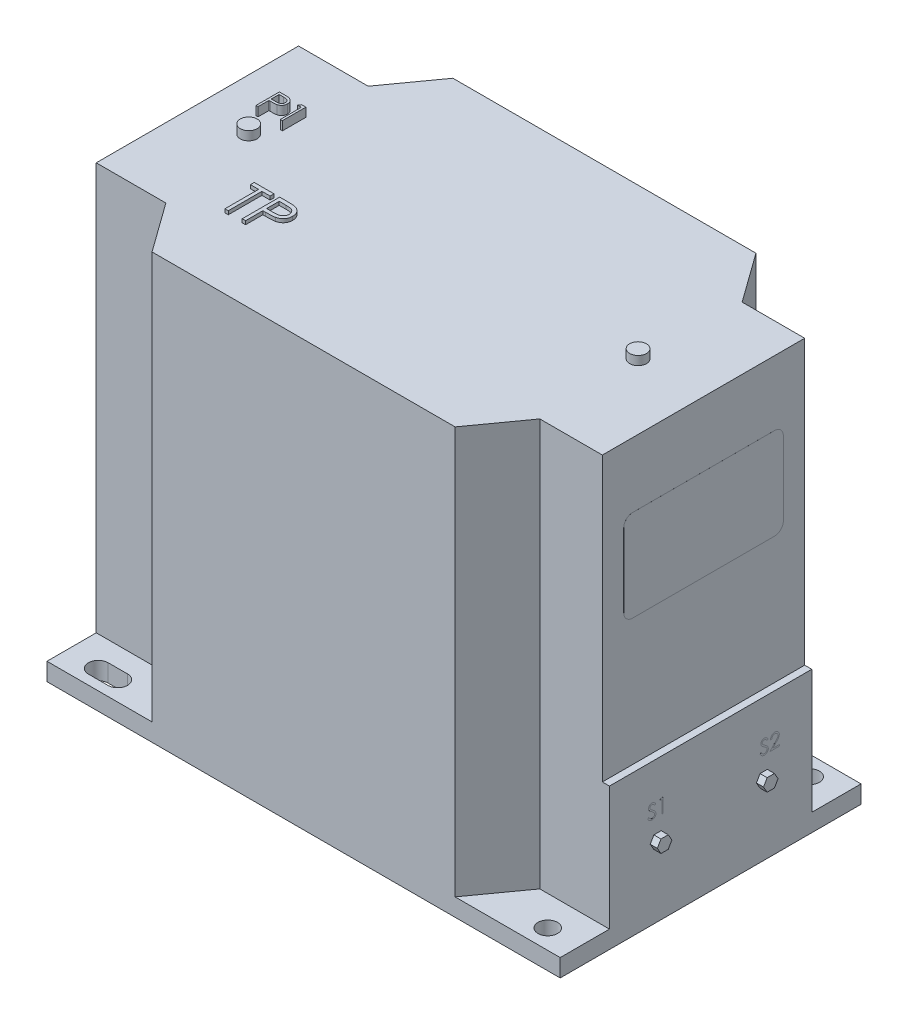
SolidWorks part; units mm, degrees
ref_plane "Alzado" through (0, 0, 0) normal (0, 0, 1) x (1, 0, 0)
ref_plane "Planta" through (0, 0, 0) normal (0, 1, 0) x (1, 0, 0)
ref_plane "Vista lateral" through (0, 0, 0) normal (1, 0, 0) x (0, 0, -1)
sketch "Croquis1" plane through (0, 0, 0) normal (0, 1, 0) x (1, 0, 0)
  line L1 (-145, 85) -> (145, 85)
  line L2 (-145, 85) -> (-145, -85)
  line L3 (-145, -85) -> (145, -85)
  line L4 (145, 85) -> (145, -85)
  line L5 (-145, 85) -> (145, -85) construction
  line L6 (-145, -85) -> (145, 85) construction
  point P0 (0, 0)
  dimension "D1" = 290
  dimension "D2" = 170
extrude "Saliente-Extruir1" add sketch "Croquis1" along normal blind 240
sketch "Croquis2" plane through (0, 240, 0) normal (0, 1, 0) x (1, 0, 0)
  line L0 (0, 0) -> (145, 0) construction
  line L1 (145, -85) -> (145, 85) construction
  line L2 (0, 0) -> (0, 85) construction
  line L3 (145, 85) -> (-145, 85) construction
  line L4 (-127, 74) -> (-116, 74) construction
  line L5 (-127, 79.5) -> (-116, 79.5)
  line L6 (-127, 68.5) -> (-116, 68.5)
  line L7 (-127, -74) -> (-116, -74) construction
  line L8 (-127, -79.5) -> (-116, -79.5)
  line L9 (-127, -68.5) -> (-116, -68.5)
  line L10 (-145, 57.1591) -> (-105.6531, 57.1591)
  line L11 (-145, 85) -> (-145, -85) construction
  line L12 (-105.6531, 57.1591) -> (-85.6261, 85)
  line L13 (145, 57.1591) -> (105.6531, 57.1591)
  line L14 (105.6531, 57.1591) -> (85.6261, 85)
  line L15 (145, -57.1591) -> (105.6531, -57.1591)
  line L16 (105.6531, -57.1591) -> (85.6261, -85)
  line L17 (-105.6531, -57.1591) -> (-85.6261, -85)
  line L18 (-145, -57.1591) -> (-105.6531, -57.1591)
  circle A0 centre (127, 74) radius 5.5
  circle A1 centre (127, -74) radius 5.5
  arc A2 (-127, 79.5) -> (-127, 68.5) centre (-127, 74) ccw
  arc A3 (-116, 68.5) -> (-116, 79.5) centre (-116, 74) ccw
  arc A4 (-127, -79.5) -> (-127, -68.5) centre (-127, -74) cw
  arc A5 (-116, -68.5) -> (-116, -79.5) centre (-116, -74) cw
  point P14 (-121.5, 74)
  point P22 (-121.5, -74)
  line M9 (145, -85) -> (145, 85)
  line M10 (145, 85) -> (-145, 85)
  line M11 (-145, 85) -> (-145, -85)
  line M12 (-145, -85) -> (145, -85)
  dimension "D1" = 11
  dimension "D2" = 74
  dimension "D3" = 127
  dimension "D4" = 11
  dimension "D5" = 254
  dimension "D6" = 11
extrude "Cortar-Extruir1" cut sketch "Croquis2" against normal blind 230 contours L18 L17 L9 A5 L8 A4 M11 M12 | L10 L12 A3 L6 A2 L5 M10 M11 | L14 L13 A0 M9 M10 | L15 L16 A1 M12 M9 region at (-144.3442, 240, -71.0796) region at (-125.3265, 240, 57.8149) region at (119.4598, 240, -71.8739) region at (119.4598, 240, 71.8739)
sketch "Croquis3" plane through (0, 240, 0) normal (0, 1, 0) x (1, 0, 0)
  line L0 (-127, 74) -> (-116, 74) construction
  line L1 (-127, 79.5) -> (-116, 79.5)
  line L2 (-127, 68.5) -> (-116, 68.5)
  line L3 (-127, -74) -> (-116, -74) construction
  line L4 (-127, -68.4262) -> (-116, -68.4262)
  line L5 (-127, -79.5738) -> (-116, -79.5738)
  arc A0 (-127, 79.5) -> (-127, 68.5) centre (-127, 74) ccw
  arc A1 (-116, 68.5) -> (-116, 79.5) centre (-116, 74) ccw
  arc A2 (-127, -68.4262) -> (-127, -79.5738) centre (-127, -74) ccw
  arc A3 (-116, -79.5738) -> (-116, -68.4262) centre (-116, -74) ccw
  circle A4 centre (127, 74) radius 5.5
  circle A5 centre (127, -74) radius 5.5
  point P4 (-121.5, 74)
  point P9 (-121.5, -74)
  dimension "D2" = 11
  dimension "D1" = 11
extrude "Cortar-Extruir3" cut sketch "Croquis3" against normal blind 309
sketch "Croquis4" plane through (145, 0, 0) normal (1, 0, 0) x (0, 0, -1)
  line L0 (-57.1591, 0) -> (-57.1591, 80)
  line L1 (-85, 0) -> (85, 0) construction
  line L2 (-57.1591, 10) -> (-57.1591, 240) construction
  line L3 (-57.1591, 80) -> (57.1591, 80)
  line L4 (57.1591, 10) -> (57.1591, 240) construction
  line L5 (57.1591, 80) -> (57.1591, 0)
  line L6 (57.1591, 0) -> (-57.1591, 0)
  line L7 (-57.1591, 240) -> (-57.1591, 80)
  line L8 (-57.1591, 240) -> (57.1591, 240)
  line L11 (57.1591, 240) -> (57.1591, 80)
  line M2 (57.1591, 10) -> (57.1591, 240)
  line M3 (57.1591, 240) -> (-57.1591, 240)
  line M4 (-57.1591, 240) -> (-57.1591, 10)
  dimension "D1" = 80
extrude "Cortar-Extruir4" cut sketch "Croquis4" against normal blind 4 contours L3 M4 M2 M3 region at (145, 160, 0)
sketch "Croquis5" plane through (-145, 0, 0) normal (-1, 0, 0) x (0, 0, 1)
  line L1 (43.4139, 29.4196) -> (40.9893, 33.619)
  line L2 (40.9893, 33.619) -> (36.1403, 33.619)
  line L3 (36.1403, 33.619) -> (33.7158, 29.4196)
  line L4 (33.7158, 29.4196) -> (36.1403, 25.2202)
  line L5 (36.1403, 25.2202) -> (40.9893, 25.2202)
  line L6 (40.9893, 25.2202) -> (43.4139, 29.4196)
  circle A0 centre (38.5648, 29.4196) radius 4.1994 construction
extrude "Saliente-Extruir2" add sketch "Croquis5" along normal blind 4
sketch "Croquis6" plane through (-145, 0, 0) normal (-1, 0, 0) x (0, 0, 1)
  line L0 (43.4139, 29.4196) -> (33.7158, 29.4196) construction
  line L1 (33.7158, 29.4196) -> (38.5648, 29.4196) construction
  line L2 (38.5648, 29.4196) -> (38.5648, 74.3859) construction
  line L4 (43.4139, 74.3859) -> (40.9893, 78.5853)
  line L5 (40.9893, 78.5853) -> (36.1403, 78.5853)
  line L6 (36.1403, 78.5853) -> (33.7158, 74.3859)
  line L7 (33.7158, 74.3859) -> (36.1403, 70.1865)
  line L8 (36.1403, 70.1865) -> (40.9893, 70.1865)
  line L9 (40.9893, 70.1865) -> (43.4139, 74.3859)
  circle A0 centre (38.5648, 74.3859) radius 4.1994 construction
extrude "Saliente-Extruir3" add sketch "Croquis6" along normal blind 4
sketch "Croquis7" plane through (145, 0, 0) normal (1, 0, 0) x (0, 0, -1)
  line L0 (0, 0) -> (0, 80) construction
  line L1 (-85, 0) -> (85, 0) construction
  line L2 (-57.1591, 80) -> (57.1591, 80) construction
  line L3 (0, 40) -> (30, 40) construction
  line L4 (-27.9449, 36.4404) -> (-32.0551, 36.4404)
  line L5 (34.1103, 40) -> (32.0551, 43.5596)
  line L6 (32.0551, 43.5596) -> (27.9449, 43.5596)
  line L7 (27.9449, 43.5596) -> (25.8897, 40)
  line L8 (25.8897, 40) -> (27.9449, 36.4404)
  line L9 (27.9449, 36.4404) -> (32.0551, 36.4404)
  line L10 (32.0551, 36.4404) -> (34.1103, 40)
  line L11 (-32.0551, 36.4404) -> (-34.1103, 40)
  line L12 (-34.1103, 40) -> (-32.0551, 43.5596)
  line L13 (-32.0551, 43.5596) -> (-27.9449, 43.5596)
  line L14 (-27.9449, 43.5596) -> (-25.8897, 40)
  line L15 (-25.8897, 40) -> (-27.9449, 36.4404)
  circle A0 centre (30, 40) radius 3.5596 construction
  dimension "D1" = 30
extrude "Saliente-Extruir5" add sketch "Croquis7" along normal blind 4
sketch "Croquis8" plane through (145, 0, 0) normal (1, 0, 0) x (0, 0, -1)
  text T0 "              \r\n\r\n       S1                 S2" font "Century Gothic" height in points 30
extrude "Saliente-Extruir6" add sketch "Croquis8" along normal blind 0.01
sketch "Croquis9" plane through (-145, 0, 0) normal (-1, 0, 0) x (0, 0, 1)
  text T0 "\r\n\r\n\r\n\r\n\r\n\r\n                P2\r\n                                                  \r\n" font "Century Gothic" height in points 50
extrude "Saliente-Extruir7" add sketch "Croquis9" along normal blind 0.01
sketch "Croquis10" plane through (141, 0, 0) normal (1, 0, 0) x (0, 0, -1)
  line L1 (-40.0867, 203.3344) -> (40.0867, 203.3344)
  line L2 (-45.0867, 198.3344) -> (-45.0867, 156.662)
  line L3 (-40.0867, 151.662) -> (40.0867, 151.662)
  line L4 (45.0867, 198.3344) -> (45.0867, 156.662)
  line L5 (-45.0867, 203.3344) -> (45.0867, 151.662) construction
  line L6 (-45.0867, 151.662) -> (45.0867, 203.3344) construction
  arc A0 (40.0867, 203.3344) -> (45.0867, 198.3344) centre (40.0867, 198.3344) cw
  arc A1 (40.0867, 151.662) -> (45.0867, 156.662) centre (40.0867, 156.662) ccw
  arc A2 (-45.0867, 156.662) -> (-40.0867, 151.662) centre (-40.0867, 156.662) ccw
  arc A3 (-40.0867, 203.3344) -> (-45.0867, 198.3344) centre (-40.0867, 198.3344) ccw
  point P0 (0, 177.4982)
  dimension "D1" = 5
extrude "Saliente-Extruir8" add sketch "Croquis10" along normal blind 0.01
sketch "Croquis11" plane through (0, 240, 0) normal (0, 1, 0) x (1, 0, 0)
  line L0 (-145, 0) -> (141, 0) construction
  line L1 (141, -57.1591) -> (141, 57.1591) construction
  line L2 (-145, 57.1591) -> (-145, -57.1591) construction
  circle A0 centre (-116, 0) radius 4.75
  circle A1 centre (104, 0) radius 4.75
  text T0 " \r\n\r\n    P1" font "Century Gothic" height in points 50
  dimension "D1" = 9.5
  dimension "D2" = 9.5
  dimension "D3" = 110
  dimension "D4" = 110
extrude "Saliente-Extruir9" add sketch "Croquis11" along normal blind 5
sketch "Croquis12" plane through (-145, 0, 0) normal (-1, 0, 0) x (0, 0, 1)
  line L1 (5.8053, 35.8489) -> (25.2829, 35.8489)
  line L2 (5.8053, 35.8489) -> (5.8053, 33.9011)
  line L3 (5.8053, 33.9011) -> (25.2829, 33.9011)
  line L4 (25.2829, 35.8489) -> (25.2829, 33.9011)
  line L5 (5.8053, 35.8489) -> (25.2829, 33.9011) construction
  line L6 (5.8053, 33.9011) -> (25.2829, 35.8489) construction
  line L7 (8.1682, 33.1073) -> (22.92, 33.1073)
  line L8 (8.1682, 33.1073) -> (8.1682, 31.2782)
  line L9 (8.1682, 31.2782) -> (22.92, 31.2782)
  line L10 (22.92, 33.1073) -> (22.92, 31.2782)
  line L11 (8.1682, 33.1073) -> (22.92, 31.2782) construction
  line L12 (8.1682, 31.2782) -> (22.92, 33.1073) construction
  line L13 (12.9314, 26.6468) -> (18.1568, 26.6468)
  line L14 (12.9314, 26.6468) -> (12.9314, 25.4007)
  line L15 (12.9314, 25.4007) -> (18.1568, 25.4007)
  line L16 (18.1568, 26.6468) -> (18.1568, 25.4007)
  line L17 (12.9314, 26.6468) -> (18.1568, 25.4007) construction
  line L18 (12.9314, 25.4007) -> (18.1568, 26.6468) construction
  line L19 (14.5892, 59.0604) -> (16.499, 59.0604)
  line L20 (14.5892, 59.0604) -> (14.5892, 36.572)
  line L21 (14.5892, 36.572) -> (16.499, 36.572)
  line L22 (16.499, 59.0604) -> (16.499, 36.572)
  line L23 (14.5892, 59.0604) -> (16.499, 36.572) construction
  line L24 (14.5892, 36.572) -> (16.499, 59.0604) construction
  line L25 (10.525, 30.3038) -> (20.5632, 30.3038)
  line L26 (10.525, 30.3038) -> (10.525, 28.6247)
  line L27 (10.525, 28.6247) -> (20.5632, 28.6247)
  line L28 (20.5632, 30.3038) -> (20.5632, 28.6247)
  line L29 (10.525, 30.3038) -> (20.5632, 28.6247) construction
  line L30 (10.525, 28.6247) -> (20.5632, 30.3038) construction
  point P0 (15.5441, 34.875)
  point P5 (15.5441, 26.0237)
  point P6 (15.5441, 32.1928)
  point P15 (15.5441, 47.8162)
  point P22 (15.5441, 29.4643)
extrude "Saliente-Extruir10" add sketch "Croquis12" along normal blind 0.1
sketch "Croquis13" plane through (0, 240, 0) normal (0, 1, 0) x (1, 0, 0)
  line L0 (-89.0341, -45.2846) -> (110.5251, -45.2846) construction
  text T0 "TP" font "Century Gothic" height in points 80
extrude "Saliente-Extruir11" add sketch "Croquis13" along normal blind 2
ref_plane "Plano1" through (0, 0, 0) normal (0, 0, 1) x (1, 0, 0)
